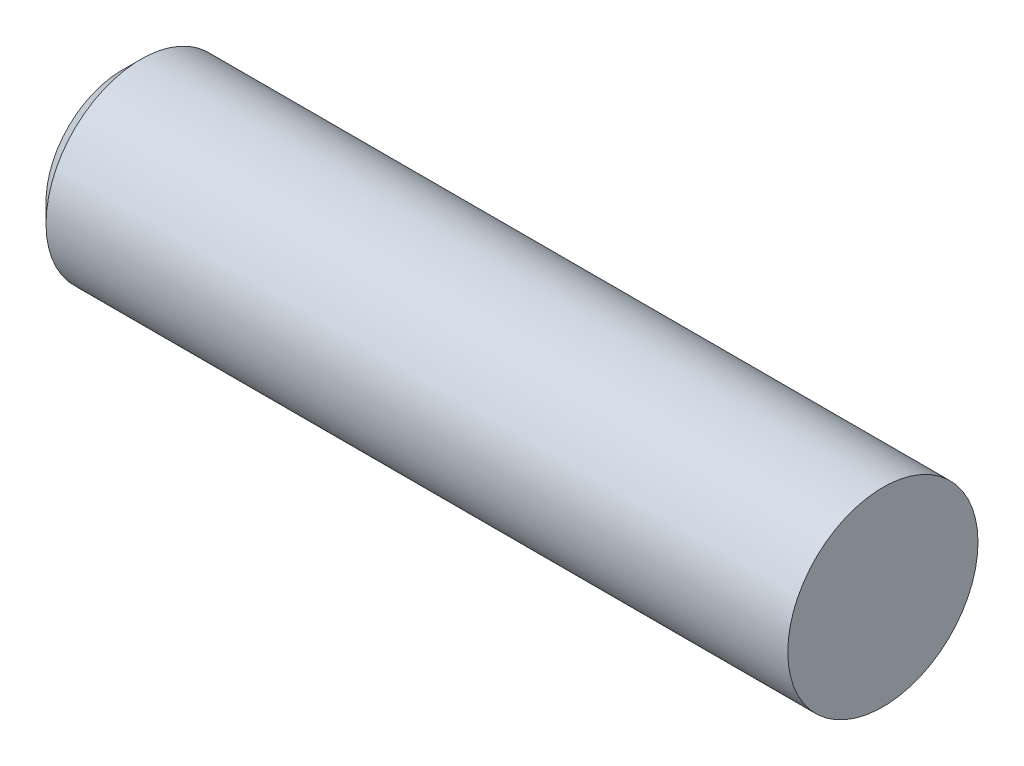
SolidWorks part; units mm, degrees
material "Cast Alloy Steel"
ref_plane "Front" through (0, 0, 0) normal (0, 0, 1) x (1, 0, 0)
ref_plane "Top" through (0, 0, 0) normal (0, 1, 0) x (1, 0, 0)
ref_plane "Right" through (0, 0, 0) normal (1, 0, 0) x (0, 0, -1)
sketch "Sketch1" plane through (0, 0, 0) normal (0, 0, 1) x (1, 0, 0)
  line L0 (-6.35, 0) -> (6.35, 0) construction
  line L1 (6.35, 1.5875) -> (6.35, -1.5875) construction
  line L2 (-6.35, 1.5875) -> (-6.35, -1.5875) construction
  dimension "Length" = 12.7
  dimension "Diameter" = 3.175
sketch "Sketch2" plane through (0, 0, 0) normal (1, 0, 0) x (0, 0, -1)
  circle A0 centre (0, 0) radius 1.5875
extrude "Extrude1" add sketch "Sketch2" against normal up to vertex (6.35 mm away) and the other way up to vertex (6.35 mm away) up to point (-6.35, 1.5875, 0) other way up to point (6.35, 1.5875, 0)
chamfer "Chamfer1" distance 0.3175 angle 45 2 edges at (6.35, 0, -1.5875) (-6.35, 0, -1.5875)
other "DeleteFace1" face at (6.0325, 0, -1.5875) and patch yes
equation "\"D1@Chamfer1\" = \"Diameter@Sketch1\"*.1"
